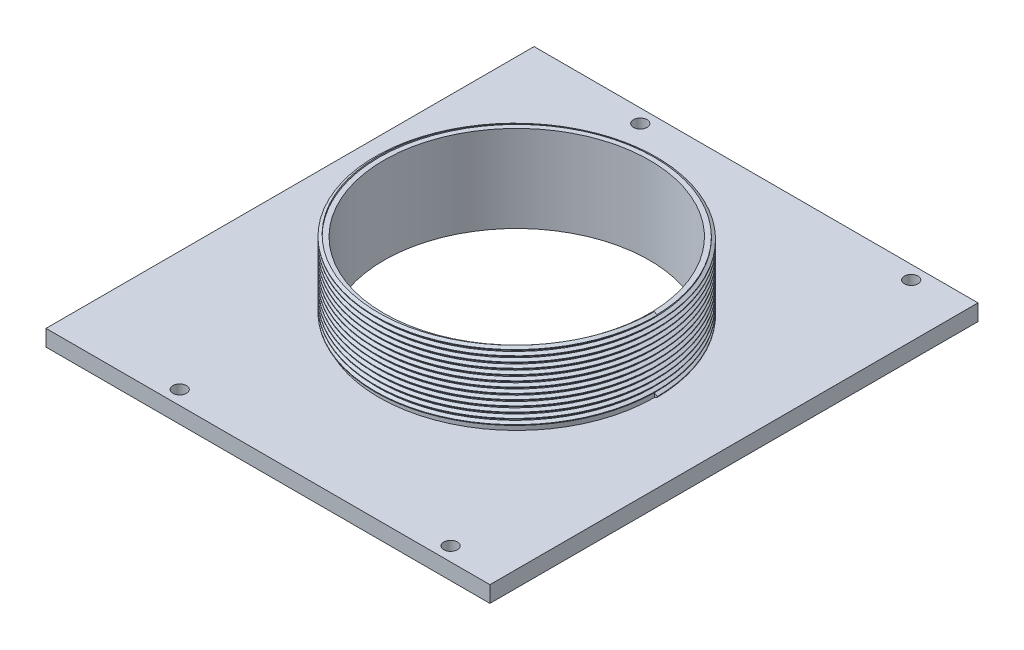
SolidWorks part; units mm, degrees
ref_plane "前视基准面" through (0, 0, 0) normal (0, 0, 1) x (1, 0, 0)
ref_plane "上视基准面" through (0, 0, 0) normal (0, 1, 0) x (1, 0, 0)
ref_plane "右视基准面" through (0, 0, 0) normal (1, 0, 0) x (0, 0, -1)
ref_plane "基准面1" through (0, 262.2302, 0) normal (0, 1, 0) x (1, 0, 0)
sketch "草图1" plane through (0, 262.2302, 0) normal (0, 1, 0) x (1, 0, 0)
  line L6 (154.8436, -11.3716) -> (236.7706, -11.3716)
  line L7 (154.8436, -11.3716) -> (154.8436, -101.4473)
  line L8 (154.8436, -101.4473) -> (236.7706, -101.4473)
  line L9 (236.7706, -11.3716) -> (236.7706, -101.4473)
extrude "凸台-拉伸2" add sketch "草图1" against normal blind 3
sketch "草图3" plane through (0, 262.2302, 0) normal (0, 1, 0) x (1, 0, 0)
  circle A0 centre (176.9436, -13.8716) radius 1.25
  circle A1 centre (226.9436, -13.8716) radius 1.25
  circle A2 centre (176.9436, -98.8716) radius 1.25
  circle A3 centre (226.9436, -98.8716) radius 1.25
hole_wizard "M3 螺纹孔的螺纹孔钻头1" positions "草图11" profile "草图12" hole size "M3" standard "ISO" end condition through all
sketch "草图11" plane through (0, 262.2302, 0) normal (0, 1, 0) x (1, 0, 0)
  point P0 (176.9436, -13.8716)
  point P3 (226.9436, -13.8716)
  point P6 (226.9436, -98.8716)
  point P9 (176.9436, -98.8716)
sketch "草图12" plane through (176.9436, 262.2302, 13.8716) normal (1, 0, 0) x (0, 0, 1)
  line L0 (0, 0) -> (0, 3)
  line L1 (0, 3) -> (1.25, 3)
  line L2 (1.25, 3) -> (1.25, 0)
  line L5 (1.25, 0) -> (0, 0)
  line L11 (0, -6.35) -> (0, 107.95) construction
  dimension "通孔孔直径" = 2.5
  dimension "通孔孔深度" = 3
sketch "草图13" plane through (0, 262.2302, 0) normal (0, 1, 0) x (1, 0, 0)
  circle A0 centre (196.6436, -56.3716) radius 24.5
  circle A1 centre (196.6436, -56.3716) radius 25.4
extrude "切除-拉伸1" cut sketch "草图13" against normal mid plane 10 contours A0
sketch "草图14" plane through (0, 262.2302, 0) normal (0, 1, 0) x (1, 0, 0)
  circle A0 centre (196.6436, -56.3716) radius 25.4
extrude "凸台-拉伸3" add sketch "草图14" along normal blind 13
sketch "草图15" plane through (0, 275.2302, 0) normal (0, 1, 0) x (1, 0, 0)
  circle A0 centre (196.6436, -56.3716) radius 24.5
extrude "切除-拉伸2" cut sketch "草图15" against normal up to next
thread "螺纹线1" pitch 1 method extrude profile "螺纹线轮廓1" start angle 0, offset 0, length 0, pitch 1, diameter 50.8
ref_plane "基准面2" through (222.0436, 262.2302, 56.3716) normal (0, 0, 1) x (1, 0, 0)
sketch "螺纹线轮廓1" plane through (222.0436, 262.2302, 56.3716) normal (0, 0, 1) x (1, 0, 0)
  line L0 (0, 0) -> (0, 1) construction
  line L1 (0, 0) -> (0.5413, 0.3125)
  line L2 (0.5413, 0.3125) -> (0.5413, 0.4375)
  line L3 (0.5413, 0.4375) -> (0, 0.75)
  line L4 (0.5413, 0.375) -> (0, 0.375) construction
  line L11 (0, 0) -> (0, 0.75)
  point P2 (0, 0)
  dimension "Pitch" = 1
  dimension "Profile_Angle" = 60
  dimension "Profile_Land" = 0.125
  dimension "Profile_Height" = 0.5413
